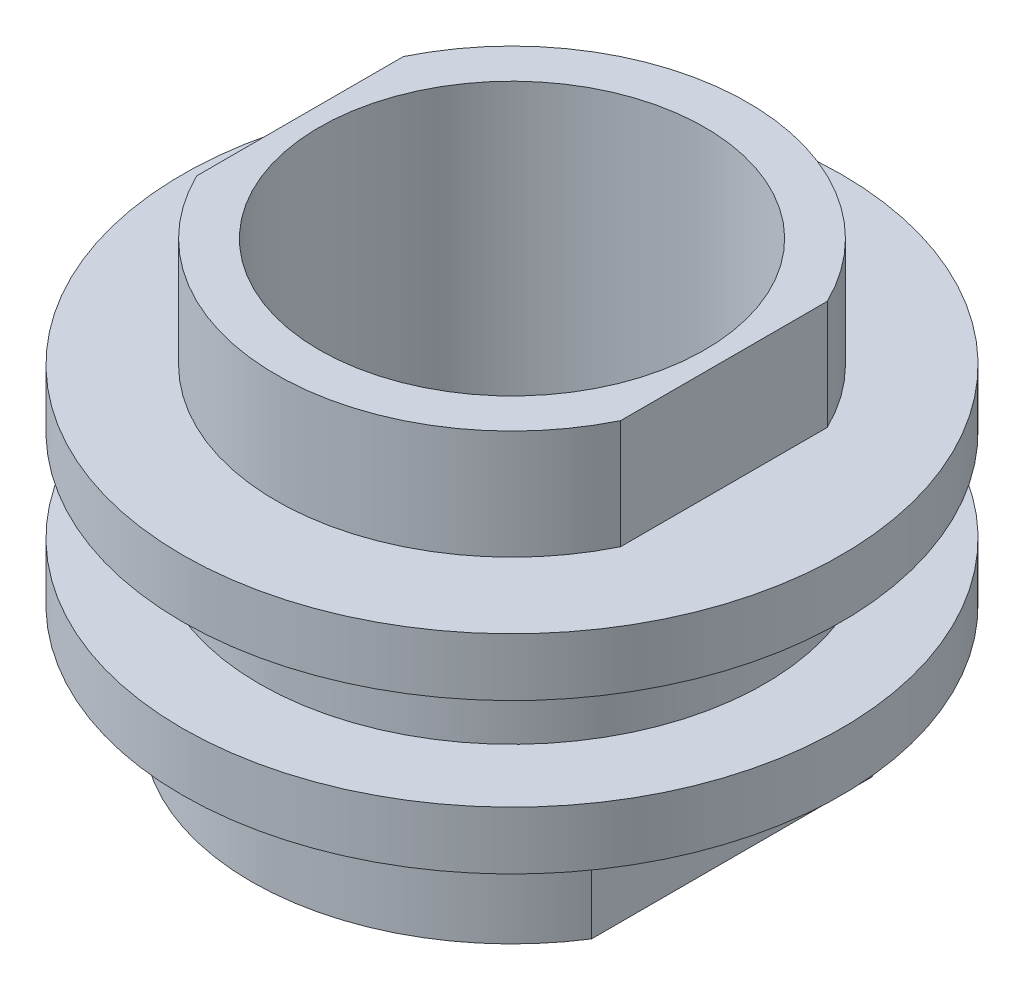
SolidWorks part; units mm, degrees
material "1060 Alloy"
ref_plane "Front Plane" through (0, 0, 0) normal (0, 0, 1) x (1, 0, 0)
ref_plane "Top Plane" through (0, 0, 0) normal (0, 1, 0) x (1, 0, 0)
ref_plane "Right Plane" through (0, 0, 0) normal (1, 0, 0) x (0, 0, -1)
sketch "Sketch1" plane through (0, 0, 0) normal (0, 1, 0) x (1, 0, 0)
  circle A0 centre (0, 0) radius 4.625
  dimension "D1" = 9.25
extrude "Boss-Extrude1" add sketch "Sketch1" along normal mid plane 1.69 contours A0
sketch "Sketch2" plane through (0, 0.845, 0) normal (0, 1, 0) x (1, 0, 0)
  circle A0 centre (0, 0) radius 6.035
  dimension "D1" = 12.07
extrude "Boss-Extrude2" add sketch "Sketch2" along normal blind 1.06 contours A0
sketch "Sketch3" plane through (0, -0.845, 0) normal (0, -1, 0) x (1, 0, 0)
  circle A0 centre (0, 0) radius 6.035
extrude "Boss-Extrude3" add sketch "Sketch3" along normal blind 1.06
sketch "Sketch4" plane through (0, 1.905, 0) normal (0, 1, 0) x (1, 0, 0)
  line L0 (-3.8813, 0) -> (-3.8813, 1.8922)
  line L1 (-3.8813, 1.8922) -> (-3.8813, -1.8922)
  line L2 (3.8813, 0) -> (3.8813, 1.8922)
  line L3 (3.8813, 1.8922) -> (3.8813, -1.8922)
  arc A0 (-3.8813, -1.8922) -> (3.8813, -1.8922) centre (0, 0) ccw
  arc A2 (3.8813, 1.8922) -> (-3.8813, 1.8922) centre (0, 0) ccw
  dimension "D1" = 8.636
extrude "Boss-Extrude4" add sketch "Sketch4" along normal blind 2 contours L2 A2 L0 L1 A0 L3 region at (0, 1.905, 0)
sketch "Sketch5" plane through (0, -1.905, 0) normal (0, -1, 0) x (1, 0, 0)
  line L0 (-4.0248, 0) -> (-4.0248, 2.5697)
  line L1 (-4.0248, 2.5697) -> (-4.0248, -2.5697)
  line L2 (4.0248, 0) -> (4.0248, 2.5697)
  line L3 (4.0248, 2.5697) -> (4.0248, -2.5697)
  arc A0 (-4.0248, -2.5697) -> (4.0248, -2.5697) centre (0, 0) ccw
  arc A2 (4.0248, 2.5697) -> (-4.0248, 2.5697) centre (0, 0) ccw
  dimension "D1" = 9.5504
extrude "Boss-Extrude5" add sketch "Sketch5" along normal blind 2 contours L2 A2 L0 L1 A0 L3 region at (0, -1.905, 0)
sketch "Sketch6" plane through (0, 3.905, 0) normal (0, 1, 0) x (1, 0, 0)
  circle A0 centre (0, 0) radius 3.5306
  dimension "D1" = 7.0612
extrude "Cut-Extrude1" cut sketch "Sketch6" against normal through all
